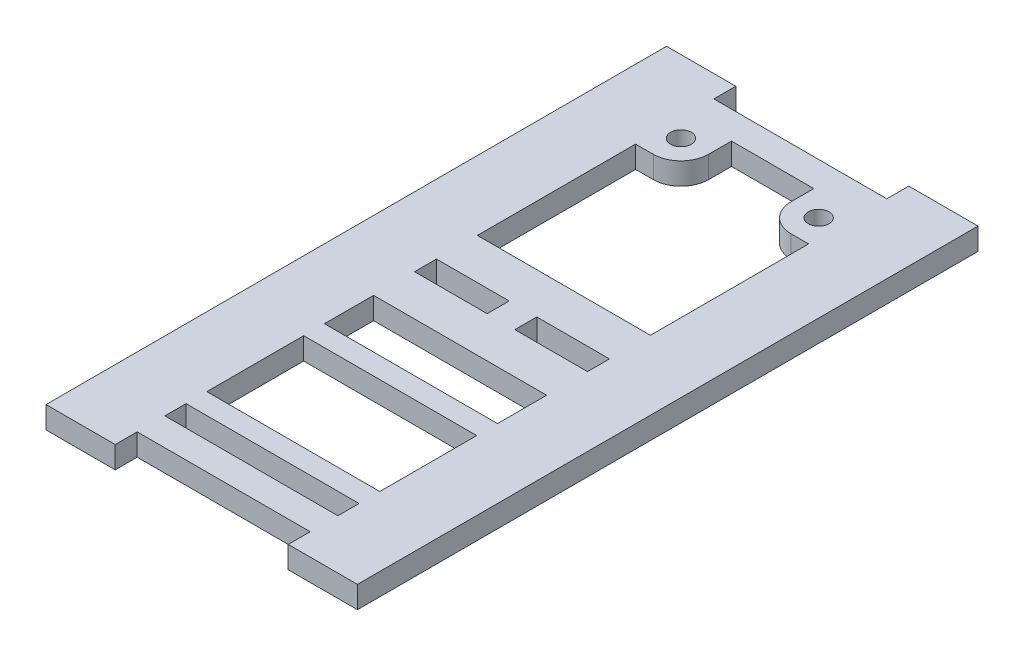
SolidWorks part; units mm, degrees
material "Birch Plywood"
ref_plane "Front Plane" through (0, 0, 0) normal (0, 0, 1) x (1, 0, 0)
ref_plane "Top Plane" through (0, 0, 0) normal (0, 1, 0) x (1, 0, 0)
ref_plane "Right Plane" through (0, 0, 0) normal (1, 0, 0) x (0, 0, -1)
other "Center of Mass"
sketch "Sketch1" plane through (0, 0, 0) normal (0, 0, 1) x (1, 0, 0)
  line L0 (-27.5, 19.2) -> (-27.5, 22.375) construction
  line L1 (-17.5, 22.375) -> (-17.5, 19.2) construction
  line L2 (-17.5, 19.2) -> (-27.5, 19.2) construction
  line L3 (-27.5, 22.375) -> (-17.5, 22.375) construction
  line L4 (-52.5, 22.375) -> (-52.5, 19.2) construction
  line L5 (-52.5, 19.2) -> (-62.5, 19.2) construction
  line L6 (-62.5, 22.375) -> (-52.5, 22.375) construction
  line L7 (-62.5, 19.2) -> (-62.5, 22.375) construction
  line L8 (-17.5, 19.2) -> (-27.5, 19.2)
  line L9 (-17.5, 22.375) -> (-17.5, 19.2)
  line L10 (-27.5, 22.375) -> (-17.5, 22.375)
  line L11 (-27.5, 19.2) -> (-27.5, 22.375)
  line L12 (-62.5, 19.2) -> (-62.5, 22.375)
  line L13 (-62.5, 22.375) -> (-52.5, 22.375)
  line L14 (-52.5, 22.375) -> (-52.5, 19.2)
  line L15 (-52.5, 19.2) -> (-62.5, 19.2)
extrude "Boss-Extrude1" add sketch "Sketch1" against normal up to surface (89.675 mm away)
sketch "Sketch2" plane through (0, 22.375, 0) normal (0, 1, 0) x (1, 0, 0)
  line L0 (-27.5, 86.5) -> (-52.5, 86.5)
  line L1 (-52.5, 86.5) -> (-52.5, 82.5)
  line L2 (-52.5, 89.675) -> (-52.5, 0) construction
  line L3 (-52.5, 82.5) -> (-27.5, 82.5)
  line L4 (-27.5, 89.675) -> (-27.5, 0) construction
  line L5 (-27.5, 82.5) -> (-27.5, 86.5)
  line L6 (-17.5, 44.8375) -> (-62.5, 44.8375) construction
  line L7 (-17.5, 89.675) -> (-17.5, 0) construction
  line L8 (-62.5, 89.675) -> (-62.5, 0) construction
  line L9 (-27.5, 7.175) -> (-27.5, 3.175)
  line L10 (-52.5, 7.175) -> (-27.5, 7.175)
  line L11 (-52.5, 3.175) -> (-52.5, 7.175)
  line L12 (-27.5, 3.175) -> (-52.5, 3.175)
  line L14 (-52.5, 37.3375) -> (-27.5, 37.3375)
  line L15 (-52.5, 37.3375) -> (-52.5, 52.3375)
  line L16 (-52.5, 52.3375) -> (-27.5, 52.3375)
  line L17 (-27.5, 37.3375) -> (-27.5, 52.3375)
  line L18 (-52.5, 37.3375) -> (-27.5, 52.3375) construction
  line L19 (-52.5, 52.3375) -> (-27.5, 37.3375) construction
  point P21 (-40, 44.8375)
  dimension "D1" = 4
  dimension "D2" = 15
extrude "Boss-Extrude2" add sketch "Sketch2" against normal up to surface (3.175 mm away) up to face at (-57.5, 19.2, -44.8375)
sketch "Sketch3" plane through (0, 22.375, 0) normal (0, 1, 0) x (1, 0, 0)
  line L0 (-17.5, 44.8375) -> (-62.5, 44.8375) construction
  line L1 (-40, 52.3375) -> (-40, 37.3375) construction
  line L2 (-52.5, 37.3375) -> (-52.5, 7.175) construction
  line L3 (-27.5, 7.175) -> (-52.5, 7.175) construction
  line L4 (-27.5, 37.3375) -> (-27.5, 7.175) construction
  line L5 (-52.5, 37.3375) -> (-27.5, 37.3375) construction
  line L6 (-27.5, 52.3375) -> (-52.5, 52.3375) construction
  line L7 (-52.5, 82.5) -> (-52.5, 52.3375) construction
  line L8 (-52.5, 82.5) -> (-27.5, 82.5) construction
  line L9 (-27.5, 82.5) -> (-27.5, 52.3375) construction
  line L10 (-52.5, 37.3375) -> (-52.5, 7.175) construction
  line L11 (-27.5, 7.175) -> (-52.5, 7.175) construction
  line L12 (-27.5, 37.3375) -> (-27.5, 7.175) construction
  line L13 (-52.5, 37.3375) -> (-27.5, 37.3375) construction
  line L14 (-17.5, 89.675) -> (-27.5, 89.675)
  line L15 (-27.5, 89.675) -> (-27.5, 86.5)
  line L16 (-27.5, 86.5) -> (-52.5, 86.5)
  line L17 (-52.5, 86.5) -> (-52.5, 89.675)
  line L18 (-52.5, 89.675) -> (-62.5, 89.675)
  line L19 (-62.5, 89.675) -> (-62.5, 0)
  line L20 (-62.5, 0) -> (-52.5, 0)
  line L21 (-52.5, 0) -> (-52.5, 3.175)
  line L22 (-52.5, 3.175) -> (-27.5, 3.175)
  line L23 (-27.5, 3.175) -> (-27.5, 0)
  line L24 (-27.5, 0) -> (-17.5, 0)
  line L25 (-17.5, 0) -> (-17.5, 89.675)
  line L26 (-17.5, 89.675) -> (-27.5, 89.675) construction
  line L27 (-27.5, 89.675) -> (-27.5, 86.5) construction
  line L28 (-27.5, 86.5) -> (-52.5, 86.5) construction
  line L29 (-52.5, 86.5) -> (-52.5, 89.675) construction
  line L30 (-52.5, 89.675) -> (-62.5, 89.675) construction
  line L31 (-62.5, 89.675) -> (-62.5, 0) construction
  line L32 (-62.5, 0) -> (-52.5, 0) construction
  line L33 (-52.5, 0) -> (-52.5, 3.175) construction
  line L34 (-52.5, 3.175) -> (-27.5, 3.175) construction
  line L35 (-27.5, 3.175) -> (-27.5, 0) construction
  line L36 (-27.5, 0) -> (-17.5, 0) construction
  line L37 (-17.5, 0) -> (-17.5, 89.675) construction
  line L38 (-27.5, 52.3375) -> (-52.5, 52.3375) construction
  line L39 (-52.5, 82.5) -> (-52.5, 52.3375) construction
  line L40 (-52.5, 82.5) -> (-27.5, 82.5) construction
  line L41 (-27.5, 82.5) -> (-27.5, 52.3375) construction
  line L42 (-42, 43.25) -> (-52.5, 46.425) construction
  line L52 (-27.5, 37.3375) -> (-52.5, 37.3375) construction
  line L64 (-38, 46.425) -> (-27.5, 46.425)
  line L65 (-38, 46.425) -> (-38, 43.25)
  line L66 (-38, 43.25) -> (-27.5, 43.25)
  line L67 (-27.5, 46.425) -> (-27.5, 43.25)
  line L68 (-38, 46.425) -> (-27.5, 43.25) construction
  line L69 (-38, 43.25) -> (-27.5, 46.425) construction
  line L70 (-42, 46.425) -> (-52.5, 43.25) construction
  line L71 (-52.5, 46.425) -> (-52.5, 43.25)
  line L72 (-42, 43.25) -> (-52.5, 43.25)
  line L73 (-42, 46.425) -> (-42, 43.25)
  line L74 (-42, 46.425) -> (-52.5, 46.425)
  point P12 (-32.75, 44.8375)
  point P33 (-47.25, 44.8375)
  dimension "D2" = 4
  dimension "D3" = 3.175
extrude "Cut-Extrude3" cut sketch "Sketch3" against normal up to surface (3.175 mm away) up to face at (-40, 19.2, -67.4188)
sketch "Sketch4" plane through (0, 22.375, 0) normal (0, 1, 0) x (1, 0, 0)
  line L0 (-40, 85.5) -> (-40, 72.9) construction
  line L1 (-47.8, 85.5) -> (-32.2, 85.5) construction
  line L2 (-47.8, 85.5) -> (-47.8, 72.9) construction
  line L3 (-47.8, 72.9) -> (-32.2, 72.9) construction
  line L4 (-32.2, 85.5) -> (-32.2, 72.9) construction
  line L5 (-49.95, 79.2) -> (-30.05, 79.2) construction
  line L6 (-52.5, 82.5) -> (-27.5, 82.5) construction
  line L7 (-52.5, 82.5) -> (-27.5, 82.5) construction
  line L8 (-27.5, 86.5) -> (-52.5, 86.5) construction
  line L9 (-27.5, 86.5) -> (-52.5, 86.5) construction
  line L10 (-40, 82.5) -> (-40, 86.5) construction
  line L11 (-47.8, 75.2) -> (-32.2, 75.2) construction
  line L12 (-45.95, 79.2) -> (-45.95, 82.5)
  line L13 (-49.95, 75.2) -> (-52.5, 75.2)
  line L14 (-52.5, 82.5) -> (-52.5, 52.3375) construction
  line L15 (-34.05, 79.2) -> (-34.05, 82.5)
  line L16 (-30.05, 75.2) -> (-27.5, 75.2)
  line L19 (-52.5, 44.8375) -> (-27.5, 44.8375) construction
  line L20 (-52.5, 46.425) -> (-52.5, 43.25) construction
  line L21 (-27.5, 43.25) -> (-27.5, 46.425) construction
  line L28 (-58.5, 64.3) -> (-21.5, 64.3) construction
  line L33 (-58.5, 72.9) -> (-21.5, 72.9) construction
  line L34 (-58.5, 72.9) -> (-58.5, 55.7) construction
  line L36 (-40, 30.2375) -> (-40, 10.2375) construction
  line L38 (-58.5, 55.7) -> (-21.5, 55.7) construction
  line L39 (-21.5, 72.9) -> (-21.5, 55.7) construction
  line L40 (-52.5, 37.3375) -> (-52.5, 7.175) construction
  line L41 (-52.5, 30.2375) -> (-27.5, 30.2375)
  line L42 (-52.5, 30.2375) -> (-52.5, 27.2375)
  line L43 (-52.5, 27.2375) -> (-27.5, 27.2375)
  line L44 (-27.5, 30.2375) -> (-27.5, 27.2375)
  line L45 (-27.5, 37.3375) -> (-27.5, 7.175) construction
  line L47 (-52.5, 13.2375) -> (-27.5, 13.2375)
  line L48 (-52.5, 13.2375) -> (-52.5, 10.2375)
  line L49 (-52.5, 10.2375) -> (-27.5, 10.2375)
  line L50 (-27.5, 13.2375) -> (-27.5, 10.2375)
  circle A0 centre (-49.95, 79.2) radius 1.5
  circle A1 centre (-30.05, 79.2) radius 1.5
  arc A2 (-49.95, 75.2) -> (-45.95, 79.2) centre (-49.95, 79.2) ccw
  arc A3 (-30.05, 75.2) -> (-34.05, 79.2) centre (-30.05, 79.2) cw
  point P10 (-40, 79.2)
  point P41 (-40, 72.9)
  point P53 (-40, 20.2375)
  line M26 (-27.5, 82.5) -> (-27.5, 52.3375)
  line M28 (-52.5, 52.3375) -> (-52.5, 82.5)
  line M29 (-52.5, 82.5) -> (-27.5, 82.5)
  line M31 (-27.5, 37.3375) -> (-27.5, 7.175)
  line M33 (-52.5, 7.175) -> (-52.5, 37.3375)
  dimension "D5" = 3
  dimension "D1" = 1
  dimension "D2" = 12.6
  dimension "D3" = 15.6
  dimension "D4" = 19.9
  dimension "D6" = 2.3
  dimension "D7" = 17.2
  dimension "D8" = 37
  dimension "D9" = 34.3625
  dimension "D10" = 19.4625
  dimension "D11" = 20
  dimension "D12" = 3
  dimension "D13" = 24.6
extrude "Boss-Extrude3" add sketch "Sketch4" against normal up to surface (3.175 mm away) contours L13 A2 L12 A0 M29 M28 | A3 L16 L15 A1 M26 M29 | L43 L41 M33 M31 | L49 L47 M33 M31 region at (-47.1909, 22.375, -76.4409) region at (-30.775, 22.375, -82.4019) region at (-40, 22.375, -28.7375) region at (-40, 22.375, -11.7375) up to face at (-32.75, 19.2, -44.8375)
equation "\"prop-dist-width\"= 86.5mm"
equation "\"prop-dist-length\"= 80mm"
equation "\"prop-hole-diameter\"= 11mm"
equation "\"prop-boost\"= 4.4mm"
equation "\"back-drop\"= 5mm"
equation "\"T\"= 0.125in'Material Thickness"
equation "\"tof_c2c\"= 19.9mm'Center to center distance of TOF sensor holes"
equation "\"tof_d\"= 3mm'TOF hole diameter"
equation "\"tof_w\"= 12.6mm'TOF width"
equation "\"tof_l\"= 15.6mm'TOF length"
equation "\"pin_w\"= 2.3mm'A standard IO Pin socket width"
equation "\"pin_l\"= 2.5mm'A standard IO Pin socket length"
equation "\"esp_pin_num\"= 8'Number of pins on one side of the ESP"
equation "\"esp_l\"= 40mm'ESP length"
equation "\"esp_w\"= 27mm'ESP width"
equation "\"esp_pin_inset\"= 3mm'Distance that ESP pins are inset"
equation "\"bat_l\"= 27mm'Battery length"
equation "\"bat_w\"= 20mm'Battery width"
equation "\"bat_h\"= 6mm'Battery thickness"
equation "\"boost_w\"= 17.2mm"
equation "\"boost_l\"= 37mm"
equation "\"boost_hole_inset\"= 2.2mm"
equation "\"boost_hole_dist\"= 7mm"
equation "\"boost_hole_d\"= 2mm"
equation "\"prop-dist\"= 80mm"
equation "\"prop-hole-depth\"= 9mm"
equation "\"rivet-extension\"= 12mm"
equation "\"rivet-hole-extension\"= 7mm"
equation "\"rivet-hole-diameter\"= 3.8mm"
equation "\"ski-length\"= 100mm"
equation "\"th\"= 0.125in'material thickness"
equation "\"ski-height\"= 50mm"
equation "\"ski-curve-gap\"= 80mm"
equation "\"ski-curve-height\"= \"rivet-hole-extension\""
equation "\"min-width\"= 4mm"
equation "\"prop-hole-diameter-small\"= 8.6mm"
equation "\"support_width\"= 10mm"
equation "\"support_gap\"= 25mm"
equation "\"support_height\"= 21.5mm"
equation "\"D3@Sketch3\"=\"T\""
equation "\"D2@Sketch4\"=\"tof_w\""
equation "\"D3@Sketch4\"=\"tof_l\""
equation "\"D4@Sketch4\"=\"tof_c2c\""
equation "\"D5@Sketch4\"=\"tof_d\""
equation "\"D6@Sketch4\"=\"pin_w\""
equation "\"D7@Sketch4\"=\"boost_w\""
equation "\"D8@Sketch4\"=\"boost_l\""
equation "\"D11@Sketch4\"=\"bat_w\""
